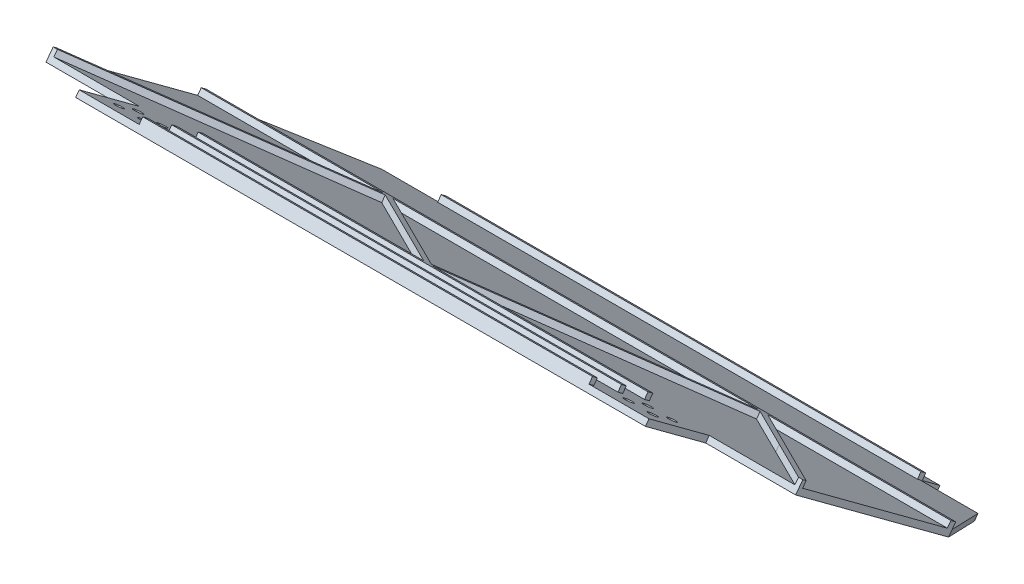
SolidWorks part; units mm, degrees
ref_plane "前视基准面" through (0, 0, 0) normal (0, 0, 1) x (1, 0, 0)
ref_plane "上视基准面" through (0, 0, 0) normal (0, 1, 0) x (1, 0, 0)
ref_plane "右视基准面" through (0, 0, 0) normal (1, 0, 0) x (0, 0, -1)
other "Configuration Table"
sketch "草图1" plane through (0, 0, 0) normal (0, 0, 1) x (1, 0, 0)
  line L11 (-17.5, -167.5) -> (167.5, -167.5)
  line L12 (-17.5, -167.5) -> (-17.5, 17.5)
  line L13 (-17.5, 17.5) -> (167.5, 17.5)
  line L14 (167.5, -167.5) -> (167.5, 17.5)
sketch "草图3" plane through (0, 0, 20) normal (0, 0, 1) x (1, 0, 0)
  line L7 (-32.4602, 32.2748) -> (182.5398, 32.2748)
  line L8 (-32.4602, 32.2748) -> (-32.4602, -182.7252)
  line L9 (-32.4602, -182.7252) -> (182.5398, -182.7252)
  line L10 (182.5398, 32.2748) -> (182.5398, -182.7252)
  point P12 (75.0398, -75.2252)
  dimension "D1" = 215
  dimension "D2" = 215
loft "放样1" add profiles "草图3", "草图1" connector at (-32.4602, 32.2748, 20) connector at (-17.5, 17.5, 0)
shell "抽壳2" thickness 3 removed face at (75.0398, -75.2252, 20)
sketch "草图4" plane through (0, 0, 3) normal (0, 0, 1) x (1, 0, 0)
  line L0 (75, 15.9864) -> (75, -182.7252)
  line L1 (166.0024, 15.9864) -> (-15.9976, 15.9864) construction
  line L2 (-32.4602, -182.7252) -> (182.5398, -182.7252) construction
  line L3 (-32.4602, -75.2252) -> (182.5398, -75.2252)
  line L4 (-32.4602, 32.2748) -> (-32.4602, -182.7252) construction
  line L5 (182.5398, -182.7252) -> (182.5398, 32.2748) construction
  circle A0 centre (66.25, -75.2252) radius 7 construction
  circle A1 centre (66.25, -75.2252) radius 4
  circle A2 centre (66.25, -68.2252) radius 1.5
  circle A3 centre (66.25, -82.2252) radius 1.5
  circle A4 centre (73.25, -75.2252) radius 1.5
  circle A5 centre (59.25, -75.2252) radius 1.5
  circle A6 centre (84.75, -75.2252) radius 1.5
  circle A7 centre (47.75, -75.2252) radius 1.5
  dimension "D1" = 8
  dimension "D2" = 14
  dimension "D3" = 3
  dimension "D4" = 3
  dimension "D5" = 3
  dimension "D6" = 3
  dimension "D7" = 3
  dimension "D8" = 3
  dimension "D9" = 37
  dimension "D10" = 18.5
extrude "切除-拉伸1" cut sketch "草图4" against normal blind 10 contours L3 A6 | L3 A6 | A3 | L3 A4 | L3 A4 | A2 | L3 A5 | L3 A5 | L3 A7 | L3 A7 region at (47.75, -74.5886, 3) region at (84.75, -74.5886, 3) region at (84.75, -75.8619, 3) region at (73.25, -74.5886, 3) region at (73.25, -75.8619, 3) region at (59.25, -74.5886, 3) region at (59.25, -75.8619, 3) region at (47.75, -75.8619, 3) region at (66.25, -68.2252, 3) region at (66.25, -82.2252, 3)
sketch "草图6" plane through (0, 0, 3) normal (0, 0, 1) x (1, 0, 0)
  line L2 (38.15, -62.5) -> (34.15, -62.5)
  line L5 (38.15, -75) -> (38.15, -62.5)
  line L6 (38.15, -75) -> (38.15, -87.5)
  line L7 (94.35, -75) -> (94.35, -62.5)
  line L8 (94.35, -75) -> (94.35, -87.5)
  line L9 (94.35, -62.5) -> (98.35, -62.5)
  line L11 (98.35, -87.5) -> (94.35, -87.5)
  line L12 (98.35, -87.5) -> (101.35, -87.5)
  line L13 (101.35, -87.5) -> (101.35, -84.5)
  line L14 (98.35, -62.5) -> (101.35, -62.5)
  line L15 (101.35, -62.5) -> (101.35, -65.5)
  line L16 (38.15, -87.5) -> (34.15, -87.5)
  line L17 (34.15, -62.5) -> (31.15, -62.5)
  line L18 (31.15, -62.5) -> (31.15, -65.5)
  line L19 (34.15, -87.5) -> (31.15, -87.5)
  line L20 (31.15, -87.5) -> (31.15, -84.5)
  line L21 (31.15, -65.5) -> (34.15, -65.5)
  line L22 (31.15, -84.5) -> (34.15, -84.5)
  line L23 (34.15, -84.5) -> (34.15, -65.5)
  line L24 (101.35, -65.5) -> (98.35, -65.5)
  line L25 (101.35, -84.5) -> (98.35, -84.5)
  line L26 (98.35, -84.5) -> (98.35, -65.5)
extrude "凸台-拉伸1" add sketch "草图6" against normal blind 40.5
sketch "草图7" plane through (98.35, 0, 0) normal (1, 0, 0) x (0, 0, -1)
  line L0 (0, -65.5) -> (0, -84.5)
  line L1 (0, -75) -> (16.5, -75)
  line L2 (16.5, -75) -> (33.5, -75)
  line L3 (33.5, -75) -> (37.5, -75)
  line L4 (37.5, -84.5) -> (37.5, -65.5) construction
  circle A0 centre (16.5, -75) radius 1.51
  circle A1 centre (33.5, -75) radius 1.51
extrude "切除-拉伸2" cut sketch "草图7" against normal blind 100 contours L2 A0 L1 | L1 A0 L2 | L3 A1 L2 | L2 A1 L3 region at (98.35, -74.3591, -16.5) region at (98.35, -74.3591, -33.5) region at (98.35, -75.6409, -33.5) region at (98.35, -75.6409, -16.5)
sketch "草图8" plane through (0, 0, 3) normal (0, 0, 1) x (1, 0, 0)
  circle A0 centre (66.25, -68.2252) radius 1.5
  circle A1 centre (59.25, -75.2252) radius 1.5
  circle A2 centre (47.75, -75.2252) radius 1.5
  circle A3 centre (73.25, -75.2252) radius 1.5
  circle A4 centre (84.75, -75.2252) radius 1.5
  circle A5 centre (66.25, -82.2252) radius 1.5
  circle M2 centre (84.75, -75.2252) radius 1.5
  circle M3 centre (59.25, -75.2252) radius 1.5
  circle M5 centre (73.25, -75.2252) radius 1.5
  circle M6 centre (66.25, -82.2252) radius 1.5
  circle M7 centre (47.75, -75.2252) radius 1.5
extrude "凸台-拉伸2" add sketch "草图8" against normal blind 3 contours M6 | M5 | M2 | M3 | M7 | A0 region at (59.25, -75.2252, 3) region at (47.75, -75.2252, 3) region at (73.25, -75.2252, 3) region at (84.75, -75.2252, 3) region at (66.25, -82.2252, 3)
sketch "草图9" plane through (0, 0, 0) normal (0, 0, -1) x (-1, 0, 0)
  line L3 (-73.5858, -76.4142) -> (0, -2.8284)
  line L4 (17.5, 17.5) -> (17.5, -167.5) construction
  line L5 (0, -2.8284) -> (0, 0)
  line L6 (-72.7486, -69.9202) -> (-2.8284, 0)
  line L7 (-167.5, 17.5) -> (17.5, 17.5) construction
  line L8 (-2.8284, 0) -> (0, 0)
  line L9 (-72.7486, -69.9202) -> (-150, -147.1716)
  line L10 (-167.5, -167.5) -> (-167.5, 17.5) construction
  line L11 (-150, -147.1716) -> (-150, -150)
  line L12 (-73.5858, -76.4142) -> (-147.1716, -150)
  line L14 (17.5, -167.5) -> (-167.5, -167.5) construction
  line L15 (-147.1716, -150) -> (-150, -150)
extrude "凸台-拉伸3" add sketch "草图9" along normal blind 4 contours L9 L11 L15 L12 L3 L5 L8 L6
sketch "草图10" plane through (0, 0, 0) normal (0, 0, -1) x (-1, 0, 0)
  line L3 (-106.6693, -40.5023) -> (-147.1716, 17.5)
  line L4 (-167.5, 17.5) -> (17.5, 17.5) construction
  line L5 (-147.1716, 17.5) -> (-167.5, 17.5)
  line L6 (-121.9738, -30.8546) -> (-167.5, 34.3423)
  line L7 (-167.5, -167.5) -> (-167.5, 17.5) construction
  line L8 (-167.5, 34.3423) -> (-167.5, 17.5)
  line L9 (-106.6693, -40.5023) -> (17.5, -218.322)
  line L10 (17.5, 17.5) -> (17.5, -167.5) construction
  line L11 (17.5, -218.322) -> (17.5, -167.5)
  line L12 (-121.9738, -30.8546) -> (-26.556, -167.5)
  line L13 (17.5, -167.5) -> (-167.5, -167.5) construction
  line L14 (-26.556, -167.5) -> (17.5, -167.5)
extrude "凸台-拉伸4" add sketch "草图10" along normal blind 4 contours L3 L5 L8 L6 L12 L14 L11 L9 rebuild error yes
sketch "草图11" plane through (0, 0, -4) normal (0, 0, -1) x (-1, 0, 0)
  line L1 (-94.35, -62.5) -> (-38.15, -62.5)
  line L2 (-94.35, -62.5) -> (-94.35, -87.5)
  line L3 (-94.35, -87.5) -> (-38.15, -87.5)
  line L4 (-38.15, -62.5) -> (-38.15, -87.5)
extrude "切除-拉伸3" cut sketch "草图11" against normal blind 4 contours L2 L1 L4 L3
sketch "草图12" plane through (0, 0, 20) normal (0, 0, 1) x (1, 0, 0)
  line L1 (182.5398, 32.2748) -> (185.5398, 32.2748)
  line L2 (182.5398, 32.2748) -> (182.5398, -182.7252)
  line L3 (182.5398, -182.7252) -> (185.5398, -182.7252)
  line L4 (185.5398, 32.2748) -> (185.5398, -182.7252)
extrude "凸台-拉伸5" add sketch "草图12" against normal blind 10 separate body
sketch "草图13" plane through (185.5398, 0, 0) normal (1, 0, 0) x (0, 0, -1)
  line L0 (-10, -182.7252) -> (-10, 32.2748) construction
  line L1 (-20, 32.2748) -> (-10, 32.2748)
  line L2 (-20, 32.2748) -> (-20, -182.7252)
  line L3 (-20, -182.7252) -> (-10, -182.7252)
  line L4 (-10, 32.2748) -> (-10, -182.7252)
extrude "切除-拉伸4" cut sketch "草图13" against normal blind 300
sketch "草图15" plane through (0, 0, -4) normal (0, 0, -1) x (-1, 0, 0)
  line L1 (-154.8521, -152.6743) -> (-38.15, -152.6743)
  line L2 (-154.8521, -152.6743) -> (-154.8521, -87.5)
  line L3 (-154.8521, -87.5) -> (-38.15, -87.5)
  line L4 (-38.15, -152.6743) -> (-38.15, -87.5)
  line L5 (-94.35, -62.5) -> (17.5, -62.5)
  line L6 (-94.35, -62.5) -> (-94.35, 17.5)
  line L7 (-94.35, 17.5) -> (17.5, 17.5)
  line L8 (17.5, -62.5) -> (17.5, 17.5)
extrude "切除-拉伸5" cut sketch "草图15" against normal blind 4 contours L6 L5 L8 L7 | L2 L1 L4 L3
sketch "草图16" plane through (0, 0, 0) normal (0, 0, -1) x (-1, 0, 0)
  line L3 (-123.7693, -120.9409) -> (-167.5, -164.6716)
  line L4 (-134.8709, -12.3007) -> (-164.6716, 17.5)
  line L5 (-167.5, 17.5) -> (17.5, 17.5) construction
  line L6 (-164.6716, 17.5) -> (-167.5, 17.5)
  line L7 (-140.0326, -12.7959) -> (-167.5, 14.6716)
  line L8 (-167.5, -167.5) -> (-167.5, 17.5) construction
  line L9 (-167.5, 14.6716) -> (-167.5, 17.5)
  line L10 (-140.0326, -12.7959) -> (14.6716, -167.5)
  line L11 (17.5, -167.5) -> (-167.5, -167.5) construction
  line L12 (14.6716, -167.5) -> (17.5, -167.5)
  line L14 (-134.8709, -12.3007) -> (17.5, -164.6716)
  line L15 (17.5, 17.5) -> (17.5, -167.5) construction
  line L16 (17.5, -164.6716) -> (17.5, -167.5)
  line L17 (-167.5, -164.6716) -> (-167.5, -167.5)
  line L18 (-116.3532, -119.1816) -> (-164.6716, -167.5)
  line L19 (-164.6716, -167.5) -> (-167.5, -167.5)
  line L20 (-116.3532, -119.1816) -> (17.5, 14.6716)
  line L21 (17.5, 14.6716) -> (17.5, 17.5)
  line L22 (-123.7693, -120.9409) -> (14.6716, 17.5)
  line L23 (14.6716, 17.5) -> (17.5, 17.5)
extrude "凸台-拉伸6" add sketch "草图16" along normal blind 4 contours L10 L22 L14 L4 L7 | L20 L10 L14 | L3 L17 L19 L18 L20 L21 L23 L22 region at (121.6045, -28.3955, 0) region at (28.3955, -121.6045, 0)
sketch "草图17" plane through (0, 0, 0) normal (0, 0, -1) x (-1, 0, 0)
  line L1 (-94.35, -62.5) -> (-38.15, -62.5)
  line L2 (-94.35, -62.5) -> (-94.35, -87.5)
  line L3 (-94.35, -87.5) -> (-38.15, -87.5)
  line L4 (-38.15, -62.5) -> (-38.15, -87.5)
extrude "切除-拉伸6" cut sketch "草图17" along normal blind 4 contours L2 L1 L4 L3
sketch "草图18" plane through (0, 0, 0) normal (0, 0, -1) x (-1, 0, 0)
  line L3 (-75, -119.25) -> (-33.5784, -119.25)
  line L7 (-65.3284, -87.5) -> (14.6716, -167.5) construction
  line L8 (-33.5784, -119.25) -> (-31.5784, -121.25)
  line L9 (-65.3284, -87.5) -> (14.6716, -167.5) construction
  line L10 (-75, -123.25) -> (-29.5784, -123.25)
  line L11 (-29.5784, -123.25) -> (-31.5784, -121.25)
  line L12 (-75, -119.25) -> (-116.4216, -119.25)
  line L13 (-164.6716, -167.5) -> (-84.6716, -87.5) construction
  line L14 (-75, -123.25) -> (-120.4216, -123.25)
  line L15 (-120.4216, -123.25) -> (-116.4216, -119.25)
  line L18 (-119.25, -75) -> (-119.25, -116.4216)
  line L19 (-90.3284, -87.5) -> (-167.5, -164.6716) construction
  line L20 (-119.25, -116.4216) -> (-121.25, -118.4216)
  line L21 (-123.25, -75) -> (-123.25, -120.4216)
  line L22 (-123.25, -120.4216) -> (-121.25, -118.4216)
  line L23 (-119.25, -75) -> (-119.25, -33.5784)
  line L24 (-167.5, 14.6716) -> (-90.3284, -62.5) construction
  line L25 (-123.25, -75) -> (-123.25, -29.5784)
  line L26 (-167.5, 14.6716) -> (-90.3284, -62.5) construction
  line L27 (-123.25, -29.5784) -> (-119.25, -33.5784)
  line L30 (-75, -30.75) -> (-116.4216, -30.75)
  line L31 (-164.6716, 17.5) -> (-84.6716, -62.5) construction
  line L32 (-75, -26.75) -> (-120.4216, -26.75)
  line L33 (-164.6716, 17.5) -> (-84.6716, -62.5) construction
  line L34 (-120.4216, -26.75) -> (-116.4216, -30.75)
  line L35 (-75, -30.75) -> (-33.5784, -30.75)
  line L36 (14.6716, 17.5) -> (-65.3284, -62.5) construction
  line L37 (-75, -26.75) -> (-29.5784, -26.75)
  line L38 (-65.3284, -62.5) -> (14.6716, 17.5) construction
  line L39 (-29.5784, -26.75) -> (-33.5784, -30.75)
  line L40 (-30.75, -33.5784) -> (-26.75, -29.5784)
  line L42 (-26.75, -75) -> (-26.75, -29.5784)
  line L43 (-59.6716, -62.5) -> (17.5, 14.6716) construction
  line L44 (-30.75, -75) -> (-30.75, -33.5784)
  line L45 (-30.75, -75) -> (-30.75, -116.4216)
  line L46 (-59.6716, -87.5) -> (17.5, -164.6716) construction
  line L47 (-26.75, -75) -> (-26.75, -120.4216)
  line L48 (-30.75, -116.4216) -> (-26.75, -120.4216)
extrude "凸台-拉伸7" add sketch "草图18" along normal blind 4
sketch "草图20" plane through (0, 0, 0) normal (0, 0, -1) x (-1, 0, 0)
  line L0 (-94.35, -62.5) -> (-94.35, -87.5)
  line L1 (-94.35, -87.5) -> (-38.15, -87.5)
  line L2 (-38.15, -87.5) -> (-38.15, -62.5)
  line L3 (-38.15, -62.5) -> (-94.35, -62.5)
  line L4 (-66.25, -75) -> (-66.25, -82)
  line L5 (-66.25, -75) -> (-47.75, -75)
  line L6 (-66.25, -75) -> (-84.75, -75)
  line L7 (-66.25, -75) -> (-66.25, -68)
  circle A0 centre (-84.75, -75) radius 1.5
  circle A1 centre (-47.75, -75) radius 1.5
  circle A2 centre (-66.25, -68) radius 1.5
  circle A3 centre (-66.25, -82) radius 1.5
extrude "切除-拉伸7" cut sketch "草图20" against normal blind 10 contours A2 | A0 | A3 | A1 region at (65.2193, -80.9693, 0) region at (47.75, -73.5424, 0) region at (86.2076, -75, 0) region at (67.2807, -66.9693, 0)
sketch "草图21" plane through (0, 0, -37.5) normal (0, 0, -1) x (-1, 0, 0)
  line L1 (-167.5, 17.5) -> (17.5, 17.5)
  line L2 (-167.5, 17.5) -> (-167.5, -167.5)
  line L3 (-167.5, -167.5) -> (17.5, -167.5)
  line L4 (17.5, 17.5) -> (17.5, -167.5)
extrude "切除-拉伸8" cut sketch "草图21" against normal blind 37.5
sketch "草图22" plane through (0, 0, 0) normal (0, 0, -1) x (-1, 0, 0)
  line L1 (17.5, 17.5) -> (-167.5, 17.5)
  line L2 (17.5, 17.5) -> (17.5, -167.5)
  line L3 (17.5, -167.5) -> (-167.5, -167.5)
  line L4 (-167.5, 17.5) -> (-167.5, -167.5)
  circle A0 centre (-66.25, -68) radius 1.5
  circle A1 centre (-66.25, -82) radius 1.5
  circle A2 centre (-84.75, -75) radius 1.5
  circle A3 centre (-47.75, -75) radius 1.5
extrude "凸台-拉伸8" add sketch "草图22" along normal blind 1 contours L2 L1 L4 L3 | A3 | A0 | A2 | A1
sketch "草图24" plane through (0, 0, 3) normal (0, 0, 1) x (1, 0, 0)
  circle A0 centre (66.25, -68) radius 3
  circle A1 centre (66.25, -82) radius 3
  circle A2 centre (47.75, -75) radius 3
  circle A3 centre (84.75, -75) radius 3
  circle M4 centre (66.25, -68) radius 1.5
  circle M5 centre (84.75, -75) radius 1.5
  circle M6 centre (66.25, -82) radius 1.5
extrude "切除-拉伸9" cut sketch "草图24" against normal blind 2 contours A0 M4 | A1 M6 | A3 M5 | A2 region at (63.3349, -68, 3) region at (63.3349, -82, 3) region at (81.8349, -75, 3)
sketch "草图25" plane through (0, 0, -1) normal (0, 0, -1) x (-1, 0, 0)
  line L0 (-167.5, 17.5) -> (17.5, -167.5)
  line L1 (-75, -75) -> (-75, -68)
  line L2 (-75, -75) -> (-75, -82)
  line L4 (-75, -75) -> (-56.5, -75)
  line L5 (-75, -75) -> (-93.5, -75)
  circle A0 centre (-75, -68) radius 1.51
  circle A1 centre (-75, -82) radius 1.51
  circle A2 centre (-93.5, -75) radius 1.51
  circle A3 centre (-56.5, -75) radius 1.51
extrude "切除-拉伸10" cut sketch "草图25" against normal blind 10 contours A2 | A0 | A1 | A3 region at (76.0375, -66.9625, -1) region at (73.9625, -80.9625, -1) region at (56.5, -73.5327, -1) region at (94.9673, -75, -1)
sketch "草图26" plane through (0, 0, -1) normal (0, 0, -1) x (-1, 0, 0)
  circle A0 centre (-84.75, -75) radius 1.5
  circle A1 centre (-66.25, -68) radius 1.5
  circle A2 centre (-66.25, -82) radius 1.5
  circle A3 centre (-47.75, -75) radius 1.5
extrude "凸台-拉伸9" add sketch "草图26" against normal blind 4 contours A0 | A1 | A2 | A3
sketch "草图28" plane through (0, 0, 3) normal (0, 0, 1) x (1, 0, 0)
  circle A0 centre (84.75, -75) radius 3
  circle A1 centre (66.25, -68) radius 3
  circle A2 centre (47.75, -75) radius 3
  circle A3 centre (66.25, -82) radius 3
extrude "凸台-拉伸10" add sketch "草图28" against normal blind 4
sketch "草图29" plane through (0, 0, 3) normal (0, 0, 1) x (1, 0, 0)
  circle A0 centre (75, -68) radius 3
  circle A1 centre (75, -82) radius 3
  circle A2 centre (93.5, -75) radius 3
  circle A3 centre (56.5, -75) radius 3
extrude "切除-拉伸11" cut sketch "草图29" against normal blind 2
sketch "草图30" plane through (0, 0, 10) normal (0, 0, 1) x (1, 0, 0)
  line L0 (-24.9801, 24.8874) -> (175.0199, -175.1126)
  line L1 (-124.9801, 124.8874) -> (-104.9801, 124.8874)
  line L2 (-104.9801, 124.8874) -> (-104.9801, 104.8874)
  line L5 (-124.9801, -75.1126) -> (-124.9801, 124.8874)
  line L6 (-124.9801, 124.8874) -> (75.0199, 124.8874)
  line L7 (275.0199, -75.1126) -> (275.0199, 124.8874)
  line L8 (275.0199, 124.8874) -> (75.0199, 124.8874)
  line L9 (-124.9801, -75.1126) -> (-124.9801, -275.1126)
  line L10 (-124.9801, -275.1126) -> (75.0199, -275.1126)
  line L12 (275.0199, -275.1126) -> (75.0199, -275.1126)
  line L13 (275.0199, -275.1126) -> (275.0199, -255.1126)
  line L14 (275.0199, -255.1126) -> (255.0199, -255.1126)
  line L16 (-104.9801, 104.8874) -> (255.0199, 104.8874)
  line L17 (-104.9801, 104.8874) -> (-104.9801, -255.1126)
  line L18 (-104.9801, -255.1126) -> (255.0199, -255.1126)
  line L19 (255.0199, 104.8874) -> (255.0199, -255.1126)
  line L20 (255.0199, 104.8874) -> (275.0199, 104.8874)
  line L21 (255.0199, 104.8874) -> (255.0199, 124.8874)
  line L22 (255.0199, 124.8874) -> (275.0199, 124.8874)
  line L23 (275.0199, 104.8874) -> (275.0199, 124.8874)
  line L24 (-104.9801, 104.8874) -> (-124.9801, 104.8874)
  line L25 (-104.9801, 104.8874) -> (-104.9801, 124.8874)
  line L26 (-104.9801, 124.8874) -> (-124.9801, 124.8874)
  line L27 (-124.9801, 104.8874) -> (-124.9801, 124.8874)
  line L28 (-104.9801, -255.1126) -> (-124.9801, -255.1126)
  line L29 (-104.9801, -255.1126) -> (-104.9801, -275.1126)
  line L30 (-104.9801, -275.1126) -> (-124.9801, -275.1126)
  line L31 (-124.9801, -255.1126) -> (-124.9801, -275.1126)
  line L32 (255.0199, -255.1126) -> (275.0199, -255.1126)
  line L33 (255.0199, -255.1126) -> (255.0199, -275.1126)
  line L34 (255.0199, -275.1126) -> (275.0199, -275.1126)
  line L35 (275.0199, -255.1126) -> (275.0199, -275.1126)
extrude "凸台-拉伸11" add sketch "草图30" along normal blind 300 separate body contours L24 L2 L1 L5 | L21 L20 L7 L8 | L29 L28 L9 L10 | L14 L33 L12 L13 region at (-114.9801, 114.8874, 10) region at (265.0199, 114.8874, 10) region at (-114.9801, -265.1126, 10) region at (265.0199, -265.1126, 10)
sketch "草图31" plane through (0, 0, 10) normal (0, 0, -1) x (-1, 0, 0)
  line L0 (-275.0199, -275.1126) -> (-255.0199, -275.1126) construction
  line L1 (-275.0199, 124.8874) -> (-255.0199, 124.8874)
  line L2 (-275.0199, 124.8874) -> (-275.0199, 104.8874)
  line L3 (-275.0199, 104.8874) -> (-255.0199, 104.8874)
  line L4 (-255.0199, 124.8874) -> (-255.0199, 104.8874)
  line L5 (104.9801, 124.8874) -> (124.9801, 124.8874)
  line L6 (104.9801, 124.8874) -> (104.9801, 104.8874)
  line L7 (104.9801, 104.8874) -> (124.9801, 104.8874)
  line L8 (124.9801, 124.8874) -> (124.9801, 104.8874)
  line L9 (104.9801, -255.1126) -> (124.9801, -255.1126)
  line L10 (104.9801, -255.1126) -> (104.9801, -275.1126)
  line L11 (104.9801, -275.1126) -> (124.9801, -275.1126)
  line L12 (124.9801, -255.1126) -> (124.9801, -275.1126)
  line L13 (-275.0199, -255.1126) -> (-255.0199, -255.1126)
  line L14 (-275.0199, -255.1126) -> (-275.0199, -275.1126)
  line L15 (-275.0199, -275.1126) -> (-255.0199, -275.1126)
  line L16 (-255.0199, -255.1126) -> (-255.0199, -275.1126)
extrude "凸台-拉伸12" add sketch "草图31" along normal blind 300
sketch "草图32" plane through (0, 11.3215, -8.3636) normal (0, 0.8043, -0.5942) x (1, 0, 0)
  line L0 (-24.9801, -22.831) -> (-19.37, -13.5065)
  line L1 (-24.9801, -22.831) -> (-104.9801, -155.7995)
  line L2 (-104.9801, -323.5478) -> (-104.9801, 159.0484) construction
  line L3 (-104.9801, -155.7995) -> (255.0199, -155.7995)
  line L4 (255.0199, -323.5478) -> (255.0199, 159.0484) construction
  line L5 (255.0199, -155.7995) -> (175.0199, -22.831)
  line L6 (169.38, -13.5065) -> (175.0199, -22.831)
  line L9 (-19.37, -13.5065) -> (169.38, -13.5065)
extrude "凸台-拉伸13" add sketch "草图32" along normal blind 2
sketch "草图33" plane through (0, 12.9301, -9.552) normal (0, 0.8043, -0.5942) x (1, 0, 0)
  line L0 (-24.9801, -22.831) -> (175.0199, -22.831)
  line L2 (170.16, -20.831) -> (173.8102, -20.831)
  line L3 (175.0199, -22.831) -> (169.38, -13.5065) construction
  line L4 (173.8102, -20.831) -> (175.0199, -22.831)
  line L5 (170.16, -20.831) -> (-23.7768, -20.831)
  line L6 (-19.37, -13.5065) -> (-104.9801, -155.7995) construction
  line L7 (-23.7768, -20.831) -> (-24.9801, -22.831)
extrude "凸台-拉伸14" add sketch "草图33" along normal blind 2
sketch "草图34" plane through (0, 92.574, 125.3137) normal (0, 0.5942, 0.8043) x (1, 0, 0)
  line L1 (-104.9801, 14.0757) -> (255.0199, 14.0757)
  line L2 (-104.9801, 14.0757) -> (-104.9801, 16.0757)
  line L3 (-104.9801, 16.0757) -> (255.0199, 16.0757)
  line L4 (255.0199, 14.0757) -> (255.0199, 16.0757)
extrude "凸台-拉伸15" add sketch "草图34" along normal blind 40
sketch "草图35" plane through (255.0199, 0, 0) normal (1, 0, 0) x (0, 0, -1)
  line L0 (-149.1232, 127.6629) -> (-145.366, 124.8874)
  line L1 (-145.366, 124.8874) -> (-142.0001, 124.8874)
  line L2 (-142.0001, 124.8874) -> (-147.9348, 129.2716)
  line L3 (-147.9348, 129.2716) -> (-149.1232, 127.6629)
extrude "切除-拉伸12" cut sketch "草图35" against normal blind 400
sketch "草图36" plane through (0, 11.3215, -8.3636) normal (0, -0.8043, 0.5942) x (1, 0, 0)
  line L1 (-104.9801, 155.7995) -> (255.0199, 155.7995)
  line L2 (-104.9801, 155.7995) -> (-104.9801, 191.1283)
  line L3 (-104.9801, 191.1283) -> (255.0199, 191.1283)
  line L4 (255.0199, 155.7995) -> (255.0199, 191.1283)
extrude "切除-拉伸13" cut sketch "草图36" against normal blind 1
sketch "草图38" plane through (0, 12.9301, -9.552) normal (0, 0.8043, -0.5942) x (1, 0, 0)
  line L0 (-104.9801, -155.7995) -> (-104.9801, -188.4209)
  line L1 (-104.9801, -172.1102) -> (255.0199, -172.1102)
  line L2 (255.0199, -188.4209) -> (255.0199, -155.7995) construction
  line L3 (255.0199, -172.1102) -> (255.0199, -155.7995)
  line L4 (255.0199, -172.1102) -> (255.0199, -188.4209)
  line L5 (255.0199, -188.4209) -> (175.0199, -188.4209)
  line L6 (-104.9801, -188.4209) -> (255.0199, -188.4209) construction
  line L7 (-104.9801, -188.4209) -> (-24.9801, -188.4209)
  line L8 (255.0199, -189.7746) -> (-104.9801, -189.7746) construction
  line L9 (175.0199, -188.4209) -> (255.0199, -188.4209)
  line L10 (175.0199, -188.4209) -> (175.0199, -155.7995)
  line L11 (175.0199, -155.7995) -> (255.0199, -155.7995)
  line L12 (255.0199, -188.4209) -> (255.0199, -155.7995)
  line L13 (175.0199, -188.4209) -> (255.0199, -188.4209)
  line L14 (175.0199, -188.4209) -> (175.0199, -189.7746)
  line L15 (175.0199, -189.7746) -> (255.0199, -189.7746)
  line L16 (255.0199, -188.4209) -> (255.0199, -189.7746)
  line L17 (-24.9801, -188.4209) -> (-104.9801, -188.4209)
  line L18 (-24.9801, -188.4209) -> (-24.9801, -155.7995)
  line L19 (-24.9801, -155.7995) -> (-104.9801, -155.7995)
  line L20 (-104.9801, -188.4209) -> (-104.9801, -155.7995)
  line L21 (-24.9801, -188.4209) -> (-104.9801, -188.4209)
  line L22 (-24.9801, -188.4209) -> (-24.9801, -189.7746)
  line L23 (-24.9801, -189.7746) -> (-104.9801, -189.7746)
  line L24 (-104.9801, -188.4209) -> (-104.9801, -189.7746)
  line M3 (-104.9801, -155.7995) -> (-104.9801, -188.4209)
  line M4 (-104.9801, -188.4209) -> (255.0199, -188.4209)
  line M5 (255.0199, -188.4209) -> (255.0199, -155.7995)
extrude "切除-拉伸16" cut sketch "草图38" against normal blind 3 contours L10 L1 M4 M5 | L11 L10 L1 M5 | L16 L14 L15 M4 | L24 L23 L22 M4 | L18 L1 L0 M4 | L18 L19 L1 M3 region at (-64.9801, 110.3499, 122.3213) region at (-64.9801, 120.0416, 135.4405) region at (-64.9801, 125.2895, 142.5445) region at (215.0199, 110.3499, 122.3213) region at (215.0199, 120.0416, 135.4405) region at (215.0199, 125.2895, 142.5445)
sketch "草图40" plane through (0, 11.3215, -8.3636) normal (0, -0.8043, 0.5942) x (1, 0, 0)
  line L0 (-24.9801, 172.787) -> (-24.9801, 152.787)
  line L1 (-24.9801, 155.7995) -> (-24.9801, 189.7746) construction
  line L2 (-24.9801, 152.787) -> (0.0199, 152.787)
  line L4 (-24.9801, 152.787) -> (-24.9801, 127.787)
  line L7 (175.0199, 189.7746) -> (175.0199, 155.7995) construction
  line L8 (175.0199, 172.787) -> (175.0199, 152.787)
  line L9 (175.0199, 152.787) -> (150.0199, 152.787)
  line L12 (175.0199, 127.787) -> (175.0199, 152.787)
  line L14 (175.0199, 127.787) -> (255.0199, 127.787)
  line L15 (175.0199, 127.787) -> (175.0199, 155.7995)
  line L16 (175.0199, 155.7995) -> (255.0199, 155.7995)
  line L17 (255.0199, 127.787) -> (255.0199, 155.7995)
  line L18 (-24.9801, 127.787) -> (-104.9801, 127.787)
  line L19 (-24.9801, 127.787) -> (-24.9801, 155.7995)
  line L20 (-24.9801, 155.7995) -> (-104.9801, 155.7995)
  line L21 (-104.9801, 127.787) -> (-104.9801, 155.7995)
  line L22 (-24.9801, 152.787) -> (175.0199, 152.787)
  line L23 (-24.9801, 152.787) -> (-24.9801, 189.7746)
  line L24 (-24.9801, 189.7746) -> (175.0199, 189.7746)
  line L25 (175.0199, 152.787) -> (175.0199, 189.7746)
  circle A0 centre (156.0199, 143.787) radius 1.5
  circle A1 centre (164.0199, 143.787) radius 1.5
  circle A2 centre (164.0199, 135.787) radius 1.5
  circle A3 centre (156.0199, 135.787) radius 1.5
  circle A4 centre (-13.9801, 143.787) radius 1.5
  circle A5 centre (-5.9801, 143.787) radius 1.5
  circle A6 centre (-13.9801, 135.787) radius 1.5
  circle A7 centre (-5.9801, 135.787) radius 1.5
  line M33 (175.0199, 22.831) -> (255.0199, 155.7995)
  line M34 (255.0199, 155.7995) -> (-104.9801, 155.7995)
  line M35 (-104.9801, 155.7995) -> (-24.9801, 22.831)
extrude "切除-拉伸17" cut sketch "草图40" against normal blind 3 contours L18 L4 L0 M34 M35 | L2 L22 L9 L8 L0 M34 | L8 L25 L24 L23 L0 M34 | L21 L18 M35 | A5 | A4 | A6 | A7 | L12 L14 L8 M33 M34 | A1 | A0 | A3 | A2 | L14 L17 M33 region at (75.0199, 113.9893, 130.6137) region at (75.0199, 103.0005, 115.7386) region at (-60.9321, 95.8998, 106.1267) region at (-99.3623, 92.7991, 101.9293) region at (210.9718, 95.8998, 106.1267) region at (249.402, 92.7991, 101.9293) region at (156.0199, 96.7578, 107.2882) region at (164.0199, 96.7578, 107.2882) region at (164.0199, 92.0043, 100.8536) region at (156.0199, 92.0043, 100.8536) region at (-13.9801, 96.7578, 107.2882) region at (-5.9801, 96.7578, 107.2882) region at (-13.9801, 92.0043, 100.8536) region at (-5.9801, 92.0043, 100.8536)
sketch "草图41" plane through (0, 11.3215, -8.3636) normal (0, -0.8043, 0.5942) x (-1, 0, 0)
  line L0 (24.9801, -152.787) -> (-175.0199, -152.787)
  line L1 (24.9801, -22.831) -> (-175.0199, -22.831)
  line L2 (-75.0199, -22.831) -> (-75.0199, -152.787)
  line L3 (-75.0199, -87.809) -> (-200.0199, -87.809)
  line L4 (-200.0199, -87.809) -> (-200.0199, -127.787)
  line L5 (-175.0199, -127.787) -> (-238.1663, -127.787) construction
  line L6 (-200.0199, -127.787) -> (-238.1663, -127.787)
  line L7 (-200.0199, -87.809) -> (-200.0199, -64.3837)
  line L8 (-238.1663, -127.787) -> (-175.0199, -22.831) construction
  line L9 (-200.0199, -64.3837) -> (-238.1663, -127.787)
  line L10 (-75.0199, -87.809) -> (49.9801, -87.809)
  line L11 (49.9801, -87.809) -> (49.9801, -127.787)
  line L12 (24.9801, -127.787) -> (88.1265, -127.787) construction
  line L13 (49.9801, -127.787) -> (88.1265, -127.787)
  line L14 (49.9801, -87.809) -> (49.9801, -64.3837)
  line L15 (24.9801, -22.831) -> (88.1265, -127.787) construction
  line L16 (49.9801, -64.3837) -> (88.1265, -127.787)
  line M11 (24.9801, -127.787) -> (88.1265, -127.787)
  line M12 (88.1265, -127.787) -> (24.9801, -22.831)
  line M14 (-175.0199, -22.831) -> (-238.1663, -127.787)
  line M15 (-238.1663, -127.787) -> (-175.0199, -127.787)
extrude "切除-拉伸18" cut sketch "草图41" against normal blind 3 contours L14 L11 M11 M12 | L4 L7 M14 M15 region at (-62.6956, 74.693, 77.4199) region at (212.7354, 74.693, 77.4199)
sketch "草图42" plane through (0, 0, -290) normal (0, 0, -1) x (-1, 0, 0)
  line L0 (104.9801, 104.8874) -> (124.9801, 104.8874) construction
  line L1 (-275.0199, 124.8874) -> (-255.0199, 124.8874)
  line L2 (-275.0199, 124.8874) -> (-275.0199, 104.8874)
  line L3 (-275.0199, 104.8874) -> (-255.0199, 104.8874)
  line L4 (-255.0199, 124.8874) -> (-255.0199, 104.8874)
  line L5 (-275.0199, -255.1126) -> (-255.0199, -255.1126)
  line L6 (-275.0199, -255.1126) -> (-275.0199, -275.1126)
  line L7 (-275.0199, -275.1126) -> (-255.0199, -275.1126)
  line L8 (-255.0199, -255.1126) -> (-255.0199, -275.1126)
  line L9 (104.9801, -255.1126) -> (124.9801, -255.1126)
  line L10 (104.9801, -255.1126) -> (104.9801, -275.1126)
  line L11 (104.9801, -275.1126) -> (124.9801, -275.1126)
  line L12 (124.9801, -255.1126) -> (124.9801, -275.1126)
  line L13 (104.9801, 124.8874) -> (124.9801, 124.8874)
  line L14 (104.9801, 124.8874) -> (104.9801, 104.8874)
  line L15 (104.9801, 104.8874) -> (124.9801, 104.8874)
  line L16 (124.9801, 124.8874) -> (124.9801, 104.8874)
  line L17 (-175.0199, 24.8874) -> (-175.0199, -175.1126) construction
  line L18 (-175.0199, 19.3468) -> (24.9801, 19.3468)
  line L19 (-175.0199, 19.3468) -> (-175.0199, -175.1126)
  line L20 (-175.0199, -175.1126) -> (24.9801, -175.1126)
  line L21 (24.9801, 19.3468) -> (24.9801, -175.1126)
extrude "切除-拉伸19" cut sketch "草图42" against normal blind 1000
sketch "草图43" plane through (0, 11.3215, -8.3636) normal (0, -0.8043, 0.5942) x (1, 0, 0)
  line L1 (-24.9801, 22.831) -> (175.0199, 22.831)
  line L2 (-24.9801, 22.831) -> (-24.9801, 12.8195)
  line L3 (-24.9801, 12.8195) -> (175.0199, 12.8195)
  line L4 (175.0199, 22.831) -> (175.0199, 12.8195)
extrude "切除-拉伸20" cut sketch "草图43" along normal blind 1000
sketch "草图44" plane through (0, 11.3215, -8.3636) normal (0, -0.8043, 0.5942) x (1, 0, 0)
  line L0 (-24.9801, 152.787) -> (175.0199, 152.787) construction
  line L1 (-24.9801, 127.787) -> (-19.9801, 127.787)
  line L2 (-24.9801, 127.787) -> (-24.9801, 152.787)
  line L3 (-24.9801, 152.787) -> (-19.9801, 152.787)
  line L4 (-19.9801, 127.787) -> (-19.9801, 152.787)
  line L6 (175.0199, 127.787) -> (170.0199, 127.787)
  line L7 (175.0199, 127.787) -> (175.0199, 152.787)
  line L8 (175.0199, 152.787) -> (170.0199, 152.787)
  line L9 (170.0199, 127.787) -> (170.0199, 152.787)
extrude "切除-拉伸21" cut sketch "草图44" against normal blind 5 contours L2 L1 L4 L3 | L7 L6 L9 L8
sketch "草图46" plane through (0, 12.9301, -9.552) normal (0, 0.8043, -0.5942) x (1, 0, 0)
  line L0 (170.0199, -127.787) -> (170.0199, -152.787) construction
  line L1 (-19.9801, -152.787) -> (170.0199, -152.787)
  line L2 (-19.9801, -152.787) -> (-19.9801, -150.787)
  line L3 (-19.9801, -150.787) -> (170.0199, -150.787)
  line L4 (170.0199, -152.787) -> (170.0199, -150.787)
  line L6 (-19.9801, -127.787) -> (170.0199, -127.787)
  line L7 (-19.9801, -127.787) -> (-19.9801, -129.787)
  line L8 (-19.9801, -129.787) -> (170.0199, -129.787)
  line L9 (170.0199, -127.787) -> (170.0199, -129.787)
  line L11 (-19.9801, -127.787) -> (-19.9801, -152.787) construction
  line L12 (-19.9801, -139.787) -> (-19.9801, -140.787)
  line L14 (-19.9801, -140.787) -> (170.0199, -140.787)
  line L15 (-19.9801, -140.787) -> (-19.9801, -138.787)
  line L16 (-19.9801, -138.787) -> (170.0199, -138.787)
  line L17 (170.0199, -140.787) -> (170.0199, -138.787)
  line M17 (-19.9801, -127.787) -> (-19.9801, -152.787)
  line M18 (-19.9801, -152.787) -> (170.0199, -152.787)
  line M19 (170.0199, -152.787) -> (170.0199, -127.787)
extrude "凸台-拉伸16" add sketch "草图46" along normal blind 2 contours L8 L6 M17 M19 | L16 L14 M17 M19 | L3 M17 M18 M19 region at (75.0199, 103.12, 112.5344) region at (75.0199, 95.9897, 102.8825) region at (75.0199, 89.4537, 94.0349)
sketch "草图47" plane through (0, 12.9301, -9.552) normal (0, 0.8043, -0.5942) x (1, 0, 0)
  line L0 (-19.9801, -152.787) -> (170.0199, -152.787) construction
  line L1 (-19.9801, -127.787) -> (0.0199, -127.787)
  line L2 (-19.9801, -127.787) -> (-19.9801, -152.787)
  line L3 (-19.9801, -152.787) -> (0.0199, -152.787)
  line L4 (0.0199, -127.787) -> (0.0199, -152.787)
  line L6 (170.0199, -127.787) -> (150.0199, -127.787)
  line L7 (170.0199, -127.787) -> (170.0199, -152.787)
  line L8 (170.0199, -152.787) -> (150.0199, -152.787)
  line L9 (150.0199, -127.787) -> (150.0199, -152.787)
extrude "切除-拉伸22" cut sketch "草图47" along normal blind 2
sketch "草图48" plane through (0, 12.9301, -9.552) normal (0, 0.8043, -0.5942) x (1, 0, 0)
  line L0 (-49.9801, -64.3837) -> (200.0199, -64.3837)
  line L1 (200.0199, -64.3837) -> (200.0199, -127.787) construction
  line L2 (-49.9801, -64.3837) -> (200.0199, -64.3837)
  line L3 (-49.9801, -64.3837) -> (-49.9801, -66.3837)
  line L4 (-49.9801, -66.3837) -> (200.0199, -66.3837)
  line L5 (200.0199, -64.3837) -> (200.0199, -66.3837)
  line M19 (200.0199, -127.787) -> (200.0199, -64.3837)
  line M23 (-49.9801, -64.3837) -> (-49.9801, -127.787)
extrude "凸台-拉伸17" add sketch "草图48" along normal blind 2 contours L4 L0 M23 M19 region at (75.0199, 51.7802, 43.0379)
sketch "草图49" plane through (0, 12.9301, -9.552) normal (0, 0.8043, -0.5942) x (1, 0, 0)
  line L3 (-18.0293, -97.7987) -> (13.9468, -66.3837)
  line L4 (-18.0293, -97.7987) -> (-48.5532, -127.787)
  line L5 (0.0199, -127.787) -> (150.0199, -127.787) construction
  line L6 (44.4707, -96.372) -> (76.4467, -127.787)
  line L8 (136.0931, -66.3837) -> (138.9468, -66.3837)
  line L9 (106.977, -97.7924) -> (76.4467, -127.787)
  line L10 (-19.9801, -127.787) -> (-49.9801, -127.787) construction
  line L11 (-48.5532, -127.787) -> (-49.9801, -127.787)
  line L12 (-19.4309, -96.372) -> (-49.9801, -126.3852)
  line L13 (-49.9801, -127.787) -> (-49.9801, -66.3837) construction
  line L14 (-49.9801, -126.3852) -> (-49.9801, -127.787)
  line L15 (-49.9801, -66.3837) -> (200.0199, -66.3837) construction
  line L16 (-19.4309, -96.372) -> (11.093, -66.3837)
  line L17 (-49.9801, -66.3837) -> (200.0199, -66.3837) construction
  line L20 (43.0691, -97.7987) -> (11.093, -66.3837)
  line L21 (44.4707, -96.372) -> (13.9468, -66.3837)
  line L22 (11.093, -66.3837) -> (12.5199, -66.3837)
  line L23 (12.5199, -66.3837) -> (13.9468, -66.3837)
  line L25 (43.0691, -97.7987) -> (73.593, -127.787)
  line L26 (105.5628, -96.3782) -> (73.593, -127.787)
  line L27 (73.593, -127.787) -> (76.4467, -127.787)
  line L33 (105.5628, -96.3782) -> (136.0931, -66.3837)
  line L36 (138.9468, -66.3837) -> (106.977, -97.7924)
  line L40 (169.4707, -96.372) -> (200.0199, -126.3852)
  line L42 (200.0199, -66.3837) -> (200.0199, -127.787) construction
  line L43 (200.0199, -126.3852) -> (200.0199, -127.787)
  line L44 (168.0691, -97.7987) -> (198.593, -127.787)
  line L45 (170.0199, -127.787) -> (200.0199, -127.787) construction
  line L46 (198.593, -127.787) -> (200.0199, -127.787)
  line L47 (169.4707, -96.372) -> (138.9468, -66.3837)
  line L48 (168.0691, -97.7987) -> (136.0931, -66.3837)
  line M25 (0.0199, -127.787) -> (150.0199, -127.787)
  line M35 (200.0199, -66.3837) -> (-49.9801, -66.3837)
  line M36 (-49.9801, -66.3837) -> (-49.9801, -127.787)
  line M37 (-49.9801, -127.787) -> (-19.9801, -127.787)
  line M45 (170.0199, -127.787) -> (200.0199, -127.787)
  line M46 (200.0199, -127.787) -> (200.0199, -66.3837)
extrude "凸台-拉伸18" add sketch "草图49" along normal blind 2 contours L3 L20 L16 L12 L4 M36 M37 | L20 L3 M35 | L26 L6 L21 L3 L20 L25 | L6 L26 M25 | L36 L48 L33 L26 L6 L9 | L48 L36 M35 | L48 L44 L40 L47 L36 M45 M46 region at (-18.9088, 70.7213, 68.6776) region at (12.5199, 52.6521, 44.218) region at (43.7697, 70.6169, 68.5362) region at (106.2699, 70.617, 68.5364) region at (137.5199, 52.6521, 44.218) region at (75.0198, 88.5819, 92.8547) region at (168.9488, 70.7214, 68.6777)
sketch "草图52" plane through (0, 14.5388, -10.7404) normal (0, 0.8043, -0.5942) x (1, 0, 0)
  line L0 (-24.9801, -22.831) -> (-4.9801, -22.831)
  line L1 (-24.9801, -22.831) -> (175.0199, -22.831) construction
  line L2 (-24.9801, -22.831) -> (-23.7768, -20.831)
  line L3 (-23.7768, -20.831) -> (-4.9801, -20.831)
  line L4 (173.8102, -20.831) -> (-23.7768, -20.831) construction
  line L5 (-4.9801, -20.831) -> (-4.9801, -22.831)
  line L6 (175.0199, -22.831) -> (155.0199, -22.831)
  line L7 (-24.9801, -22.831) -> (175.0199, -22.831) construction
  line L8 (155.0199, -22.831) -> (155.0199, -20.831)
  line L9 (173.8102, -20.831) -> (-23.7768, -20.831) construction
  line L10 (155.0199, -20.831) -> (173.8102, -20.831)
  line L11 (173.8102, -20.831) -> (175.0199, -22.831)
extrude "切除-拉伸24" cut sketch "草图52" against normal blind 2
sketch "草图53" plane through (0, 12.9301, -9.552) normal (0, 0.8043, -0.5942) x (1, 0, 0)
  line L0 (-4.9801, -21.831) -> (-24.3785, -21.831)
  line L1 (-4.9801, -22.831) -> (-4.9801, -20.831) construction
  line L2 (-19.37, -13.5065) -> (-49.9801, -64.3837) construction
  line L3 (-24.3785, -21.831) -> (-19.37, -13.5065)
  line L4 (-19.37, -13.5065) -> (-4.9801, -13.5065)
  line L5 (169.38, -13.5065) -> (-19.37, -13.5065) construction
  line L6 (-4.9801, -13.5065) -> (-4.9801, -21.831)
  line L7 (155.0199, -21.831) -> (174.415, -21.831)
  line L8 (155.0199, -20.831) -> (155.0199, -22.831) construction
  line L9 (175.0199, -22.831) -> (169.38, -13.5065) construction
  line L10 (174.415, -21.831) -> (169.38, -13.5065)
  line L11 (169.38, -13.5065) -> (155.0199, -13.5065)
  line L12 (155.0199, -13.5065) -> (155.0199, -21.831)
extrude "切除-拉伸25" cut sketch "草图53" against normal blind 2
